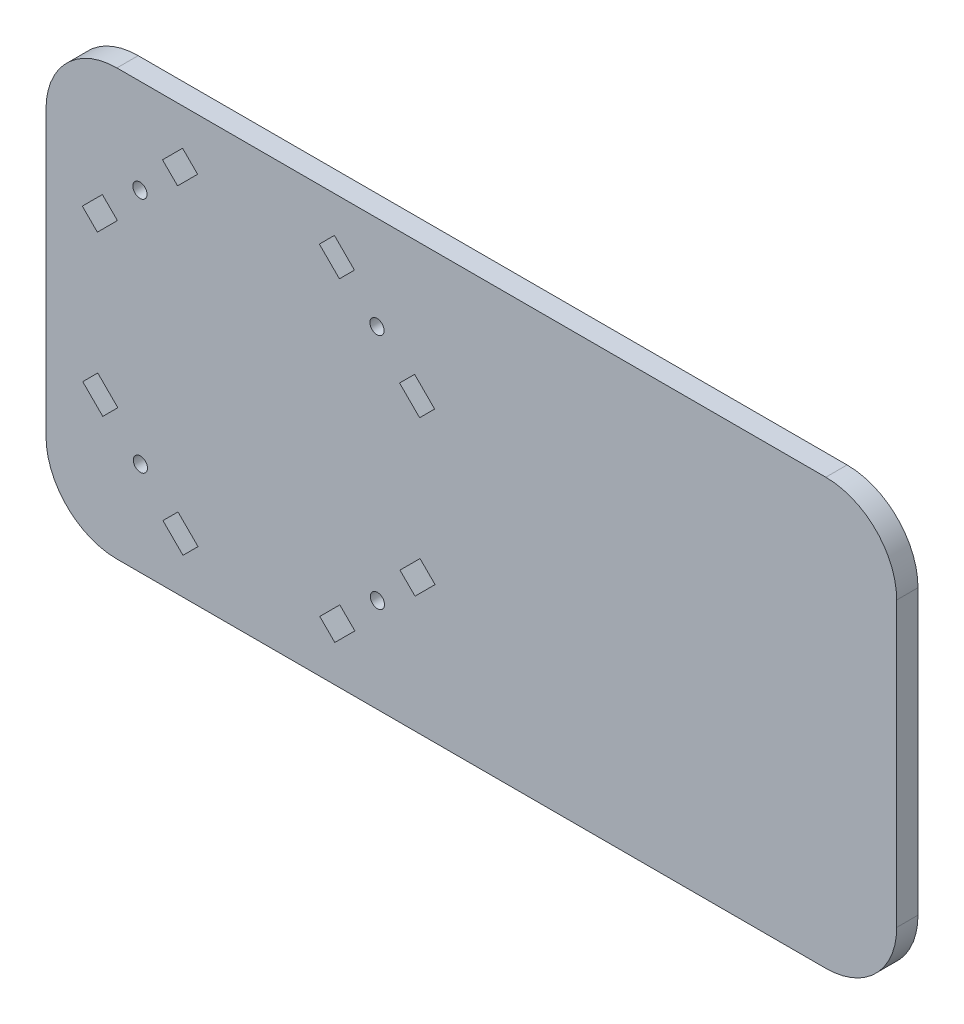
SolidWorks part; units mm, degrees
ref_plane "Plan de face" through (0, 0, 0) normal (0, 0, 1) x (1, 0, 0)
ref_plane "Plan de dessus" through (0, 0, 0) normal (0, 1, 0) x (1, 0, 0)
ref_plane "Plan de droite" through (0, 0, 0) normal (1, 0, 0) x (0, 0, -1)
sketch "Esquisse1" plane through (0, 0, 0) normal (0, 0, 1) x (1, 0, 0)
  line L0 (0, 150) -> (0, -150) construction
  line L1 (-309.6782, -150) -> (190.3218, -150)
  line L2 (-359.6782, -100) -> (-359.6782, 100)
  line L3 (-309.6782, 150) -> (190.3218, 150)
  line L4 (240.3218, -100) -> (240.3218, 100)
  arc A0 (-309.6782, -150) -> (-359.6782, -100) centre (-309.6782, -100) cw
  arc A1 (-359.6782, 100) -> (-309.6782, 150) centre (-309.6782, 100) cw
  arc A2 (190.3218, -150) -> (240.3218, -100) centre (190.3218, -100) ccw
  arc A3 (240.3218, 100) -> (190.3218, 150) centre (190.3218, 100) ccw
  point P0 (0, 0)
  dimension "D3" = 50
  dimension "D4" = 50
  dimension "D1" = 600
extrude "Boss.-Extru.1" add sketch "Esquisse1" along normal blind 15 contours L4 A3 L3 A1 L2 A0 L1 A2 region at (-59.6782, 0, 0)
sketch "Esquisse3" plane through (0, 0, 15) normal (0, 0, 1) x (1, 0, 0)
  line L0 (-263.3667, 124.106) -> (-252.7601, 113.4994)
  line L1 (-263.3667, 124.106) -> (-277.5088, 109.9639)
  line L2 (-252.7601, 113.4994) -> (-266.9022, 99.3573)
  line L3 (-277.5088, 109.9639) -> (-266.9022, 99.3573)
  line L4 (-309.3286, 56.9309) -> (-319.9352, 67.5375)
  line L5 (-309.3286, 56.9309) -> (-323.4708, 42.7887)
  line L6 (-319.9352, 67.5375) -> (-334.0774, 53.3953)
  line L7 (-323.4708, 42.7887) -> (-334.0774, 53.3953)
  line L8 (-280.3889, 70.7107) -> (-256.8823, 47.7329) construction
  line L9 (-328.7741, 48.092) -> (-258.0634, 118.8027) construction
  circle A0 centre (-293.4187, 83.4474) radius 5
  dimension "D3" = 10
  dimension "D1" = 20
  dimension "D2" = 20
extrude "Enlèv. mat.-Extru.1" cut sketch "Esquisse3" against normal through all
sketch "Esquisse4" plane through (0, 0, 15) normal (0, 0, 1) x (1, 0, 0)
  line L0 (-248.0898, 38.4115) -> (-138.9676, -70.7107) construction
  line L1 (-138.9676, 70.7107) -> (-280.3889, -70.7107) construction
  line L2 (-182.0693, 27.6089) -> (-237.2872, -27.6089) construction
  point P12 (-209.6782, 0)
ref_axis "Axe1" through (-209.6782, 0, 15) along (0, 0, -1)
pattern_circular "Répétition circulaire1" count 4 every 90 about axis through (-209.6782, 0, 15) along (0, 0, -1) of "Enlèv. mat.-Extru.1"
